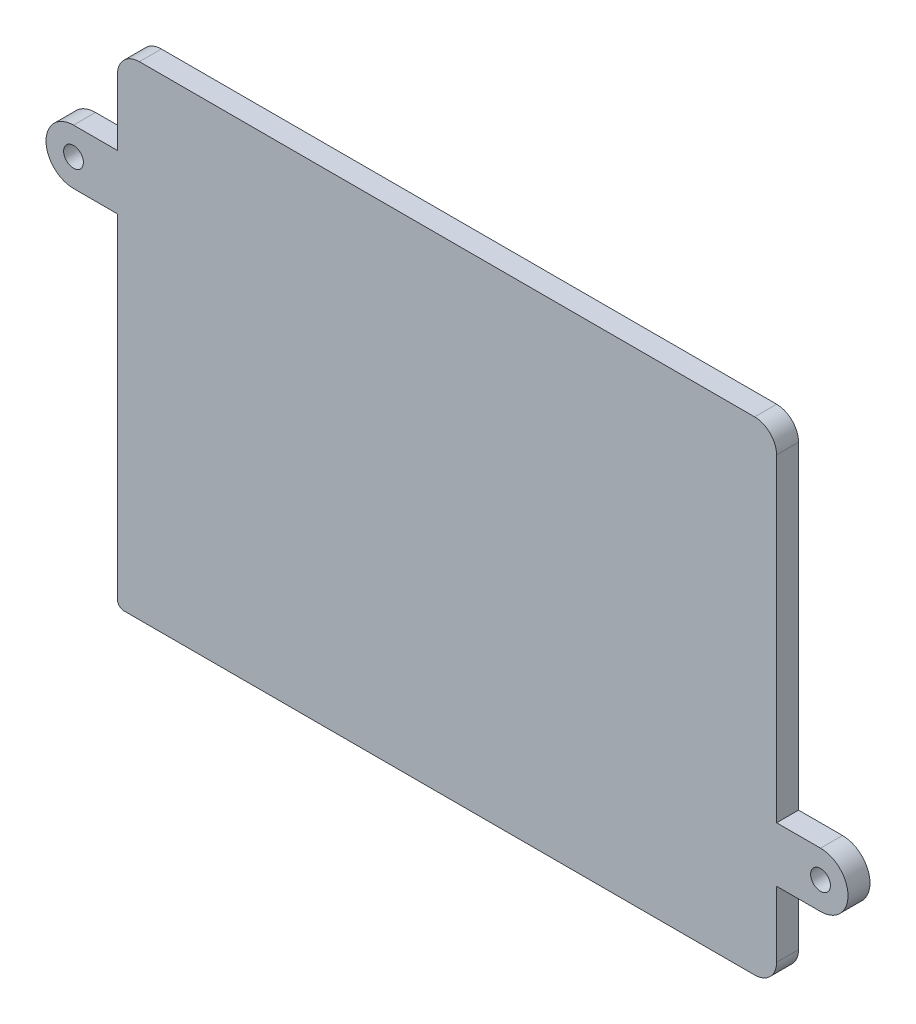
SolidWorks part; units mm, degrees
ref_plane "Front Plane" through (0, 0, 0) normal (0, 0, 1) x (1, 0, 0)
ref_plane "Top Plane" through (0, 0, 0) normal (0, 1, 0) x (1, 0, 0)
ref_plane "Right Plane" through (0, 0, 0) normal (1, 0, 0) x (0, 0, -1)
sketch "Sketch1" plane through (0, 0, 0) normal (0, 0, 1) x (1, 0, 0)
  line L0 (-85, 35) -> (-75, 35)
  line L1 (-85, 22.5) -> (-75, 22.5)
  line L2 (85, -22.5) -> (75, -22.5)
  line L3 (85, -35) -> (75, -35)
  line L4 (70, 26) -> (70, 11)
  line L5 (70, 26) -> (70, 11)
  line L6 (70, 11) -> (75, 11)
  line L7 (70, 11) -> (75, 11)
  line L36 (75, 11) -> (75, 26)
  line L38 (75, 11) -> (75, 26)
  line L39 (75, 26) -> (70, 26)
  line L40 (75, 26) -> (70, 26)
  line L84 (70, 30) -> (70, 26)
  line L85 (75, 30) -> (75, 26)
  line L86 (70, 11) -> (70, 7)
  line L87 (75, 11) -> (75, 7)
  line L102 (75, 7) -> (70, 7)
  line L103 (70, 7) -> (70, -45)
  line L104 (65, -50) -> (-65, -50)
  line L105 (-70, -45) -> (-70, 45)
  line L106 (-65, 50) -> (65, 50)
  line L107 (70, 45) -> (70, 30)
  line L108 (70, 30) -> (75, 30)
  line L109 (75, 30) -> (75, 50)
  line L110 (70, 55) -> (-70, 55)
  line L111 (-75, 50) -> (-75, 35)
  line L112 (-75, 35) -> (-85, 35)
  line L113 (-85, 22.5) -> (-75, 22.5)
  line L114 (-75, 22.5) -> (-75, -53.5)
  line L115 (-73.5, -55) -> (70, -55)
  line L116 (75, -50) -> (75, -35)
  line L117 (75, -35) -> (85, -35)
  line L118 (85, -22.5) -> (75, -22.5)
  line L119 (75, -22.5) -> (75, 7)
  line L120 (75, 7) -> (70, 7)
  line L121 (70, 7) -> (70, -45)
  line L122 (65, -50) -> (-65, -50)
  line L123 (-70, -45) -> (-70, 45)
  line L124 (-65, 50) -> (65, 50)
  line L125 (70, 45) -> (70, 30)
  line L126 (70, 30) -> (75, 30)
  line L127 (75, 30) -> (75, 50)
  line L128 (70, 55) -> (-70, 55)
  line L129 (-75, 50) -> (-75, 35)
  line L130 (-75, 35) -> (-85, 35)
  line L131 (-85, 22.5) -> (-75, 22.5)
  line L132 (-75, 22.5) -> (-75, -53.5)
  line L133 (-73.5, -55) -> (70, -55)
  line L134 (75, -50) -> (75, -35)
  line L135 (75, -35) -> (85, -35)
  line L136 (85, -22.5) -> (75, -22.5)
  line L137 (75, -22.5) -> (75, 7)
  circle A0 centre (-85, 28.75) radius 2.25
  circle A1 centre (85, -28.75) radius 2.25
  circle A2 centre (85, -28.75) radius 6.25
  circle A3 centre (-85, 28.75) radius 6.25
  arc A52 (65, -50) -> (70, -45) centre (65, -45) ccw
  arc A53 (-70, -45) -> (-65, -50) centre (-65, -45) ccw
  arc A54 (-65, 50) -> (-70, 45) centre (-65, 45) ccw
  arc A55 (70, 45) -> (65, 50) centre (65, 45) ccw
  arc A56 (75, 50) -> (70, 55) centre (70, 50) ccw
  arc A57 (-70, 55) -> (-75, 50) centre (-70, 50) ccw
  arc A58 (-85, 35) -> (-85, 22.5) centre (-85, 28.75) ccw
  arc A59 (-75, -53.5) -> (-73.5, -55) centre (-73.5, -53.5) ccw
  arc A60 (70, -55) -> (75, -50) centre (70, -50) ccw
  arc A61 (85, -35) -> (85, -22.5) centre (85, -28.75) ccw
  arc A62 (65, -50) -> (70, -45) centre (65, -45) ccw
  arc A63 (-70, -45) -> (-65, -50) centre (-65, -45) ccw
  arc A64 (-65, 50) -> (-70, 45) centre (-65, 45) ccw
  arc A65 (70, 45) -> (65, 50) centre (65, 45) ccw
  arc A66 (75, 50) -> (70, 55) centre (70, 50) ccw
  arc A67 (-70, 55) -> (-75, 50) centre (-70, 50) ccw
  arc A68 (-85, 35) -> (-85, 22.5) centre (-85, 28.75) ccw
  arc A69 (-75, -53.5) -> (-73.5, -55) centre (-73.5, -53.5) ccw
  arc A70 (70, -55) -> (75, -50) centre (70, -50) ccw
  arc A71 (85, -35) -> (85, -22.5) centre (85, -28.75) ccw
  dimension "D2" = 4.5
  dimension "D3" = 4.5
  dimension "D4" = 0
  dimension "D5" = 10
  dimension "D7" = 12.5
  dimension "D6" = 15
  dimension "D1" = 0
extrude "Boss-Extrude1" add sketch "Sketch1" along normal blind 5 contours A3 A0 | A3 L1 L0 | A2 L2 L3 | A2 A1 | L125 A65 L124 A64 L123 A63 L122 A62 L121 L86 L5 L84 | L38 L40 L5 L7 | L120 L87 L7 L86 | L126 L84 L40 L85 region at (-80, 32.9752, 0) region at (-80.7056, 33.0444, 0) region at (72.5, 28, 0) region at (72.5, 18.5, 0) region at (0, 0, 0) region at (72.5, 9, 0) region at (78.9268, -28.75, 0)
sketch "Sketch3" plane through (0, 0, 0) normal (0, 0, 1) x (1, 0, 0)
  line L8 (-65, -50) -> (65, -50)
  line L9 (70, -45) -> (70, 45)
  line L10 (-65, 50) -> (65, 50)
  line L11 (-70, 45) -> (-70, -45)
  line L12 (-68.5, 45) -> (-68.5, -45)
  line L13 (-65, -48.5) -> (65, -48.5)
  line L14 (68.5, -45) -> (68.5, 45)
  line L15 (-65, 48.5) -> (65, 48.5)
  arc A0 (70, 45) -> (65, 50) centre (65, 45) ccw construction
  arc A1 (65, -50) -> (70, -45) centre (65, -45) ccw construction
  arc A3 (-70, -45) -> (-65, -50) centre (-65, -45) ccw construction
  arc A12 (-65, 50) -> (-70, 45) centre (-65, 45) ccw construction
  arc A13 (70, 45) -> (65, 50) centre (65, 45) ccw
  arc A16 (65, -50) -> (70, -45) centre (65, -45) ccw
  arc A19 (-70, -45) -> (-65, -50) centre (-65, -45) ccw
  arc A20 (-65, 50) -> (-70, 45) centre (-65, 45) ccw
  arc A21 (-68.5, -45) -> (-65, -48.5) centre (-65, -45) ccw
  arc A22 (65, -48.5) -> (68.5, -45) centre (65, -45) ccw
  arc A23 (68.5, 45) -> (65, 48.5) centre (65, 45) ccw
  arc A24 (-65, 48.5) -> (-68.5, 45) centre (-65, 45) ccw
  dimension "D1" = 1.5
extrude "Boss-Extrude2" add sketch "Sketch3" against normal blind 2 contours L12 A24 L15 A23 L14 A22 L13 A21 region at (0, 0, 0)
